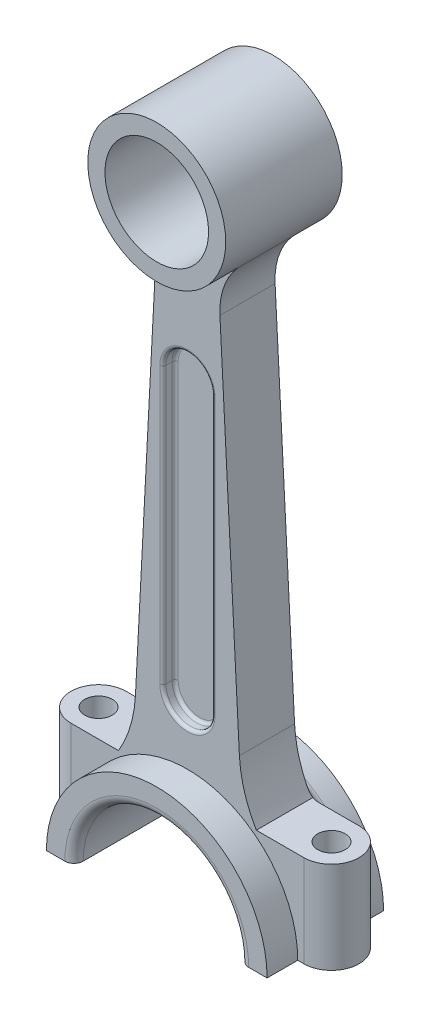
SolidWorks part; units mm, degrees
material "Cast Alloy Steel"
ref_plane "Front Plane" through (0, 0, 0) normal (0, 0, 1) x (1, 0, 0)
ref_plane "Top Plane" through (0, 0, 0) normal (0, 1, 0) x (1, 0, 0)
ref_plane "Right Plane" through (0, 0, 0) normal (1, 0, 0) x (0, 0, -1)
sketch "Sketch1" plane through (0, 0, 0) normal (0, 0, 1) x (1, 0, 0)
  line L0 (0, 0) -> (0, -201.2) construction
  line L1 (-17.8497, -169.9368) -> (-10, -20.1556)
  line L2 (17.8497, -169.9368) -> (10, -20.1556)
  line L3 (-36, -201.2) -> (-27, -201.2)
  line L4 (27, -201.2) -> (36, -201.2)
  circle A0 centre (0, 0) radius 22.5
  circle A1 centre (0, 0) radius 16.9
  arc A2 (27, -201.2) -> (-27, -201.2) centre (0, -201.2) ccw
  arc A3 (36, -201.2) -> (-36, -201.2) centre (0, -201.2) ccw
  dimension "D1" = 45
  dimension "D2" = 33.8
  dimension "D3" = 6
  dimension "D5" = 54
  dimension "D6" = 72
  dimension "D7" = 201.2
  dimension "D4" = 20
extrude "Boss-Extrude4" add sketch "Sketch1" along normal mid plane 38 contours A1 A0 | A3 A2 | L3 A2 L4 A3 region at (0, -166.005, 0) region at (-11.5231, 18.5805, 0)
extrude "Boss-Extrude5" add sketch "Sketch1<6>" along normal mid plane 18 contours A0 L0 A3 L2 | L0 A0 L1 A3 region at (7.1843, -100.8455, 0) region at (-7.1843, -100.8455, 0)
sketch "Sketch1<6>" plane through (0, 0, 0) normal (0, 0, 1) x (1, 0, 0) same geometry as "Sketch1"
sketch "Sketch4" plane through (0, 0, 9) normal (0, 0, 1) x (1, 0, 0)
  line L0 (0, 0) -> (0, -201.2) construction
  line L1 (0, -55.6) -> (0, -145.6) construction
  line L2 (8, -55.6) -> (8, -145.6)
  line L3 (-8, -55.6) -> (-8, -145.6)
  arc A0 (8, -55.6) -> (-8, -55.6) centre (0, -55.6) ccw
  arc A1 (-8, -145.6) -> (8, -145.6) centre (0, -145.6) ccw
  point P6 (0, -100.6)
extrude "Cut-Extrude1" cut sketch "Sketch4" against normal blind 4
mirror "Mirror5" about plane through (0, 0, 0) normal (0, 0, 1) of face at (0, -149.6, 7) of face at (8, -100.6, 7) of face at (0, -51.6, 7) of face at (-8, -100.6, 7) of face at (0, -100.6, 5)
fillet "Fillet1" radius 1 16 edges at (0, -153.6, -9) (-8, -100.6, -9) (0, -47.6, -9) (0, -47.6, 9) (8, -100.6, 9) (0, -153.6, 9) (-8, -100.6, -5) (0, -153.6, -5) (8, -100.6, -5) (0, -47.6, -5) (8, -100.6, 5) (0, -153.6, 5) (-8, -100.6, 5) (0, -47.6, 5) (8, -100.6, -9) (-8, -100.6, 9)
fillet "Fillet2" radius 40 2 edges at (17.8497, -169.9368, 0) (-17.8497, -169.9368, 0)
fillet "Fillet4" radius 22.5 2 edges at (-10, -20.1556, 0) (10, -20.1556, 0)
ref_plane "Plane1" through (0, -171.2, 0) normal (0, -1, 0) x (-1, 0, 0)
sketch "Sketch5" plane through (0, -171.2, 0) normal (0, -1, 0) x (-1, 0, 0)
  line L0 (-38, 0) -> (38, 0) construction
  line L1 (-38, 9) -> (38, 9)
  line L2 (-38, -9) -> (38, -9)
  arc A0 (-38, 9) -> (-38, -9) centre (-38, 0) ccw
  arc A1 (38, -9) -> (38, 9) centre (38, 0) ccw
  point P2 (0, 0)
  dimension "D1" = 9
  dimension "D2" = 76
extrude "Boss-Extrude6" add sketch "Sketch5" along normal up to surface (30 mm away) up to face at (-31.5, -201.2, 0)
sketch "Sketch6" plane through (0, 0, -9) normal (0, 0, -1) x (-1, 0, 0)
  line L1 (-27, -201.2) -> (27, -201.2)
  line L2 (-27, -201.2) -> (27, -201.2)
  arc A1 (27, -201.2) -> (-27, -201.2) centre (0, -201.2) ccw
  arc A2 (27, -201.2) -> (-27, -201.2) centre (0, -201.2) ccw
  dimension "D1" = 0
extrude "Cut-Extrude2" cut sketch "Sketch6" against normal through all contours A2 L2
sketch "Sketch7" plane through (0, -171.2, 0) normal (0, 1, 0) x (1, 0, 0)
  circle A0 centre (-38, 0) radius 4.5
  circle A1 centre (38, 0) radius 4.5
extrude "Cut-Extrude3" cut sketch "Sketch7" against normal through all
fillet "Fillet5" radius 3 2 edges at (0, -174.2, 19) (0, -165.2, -9)
